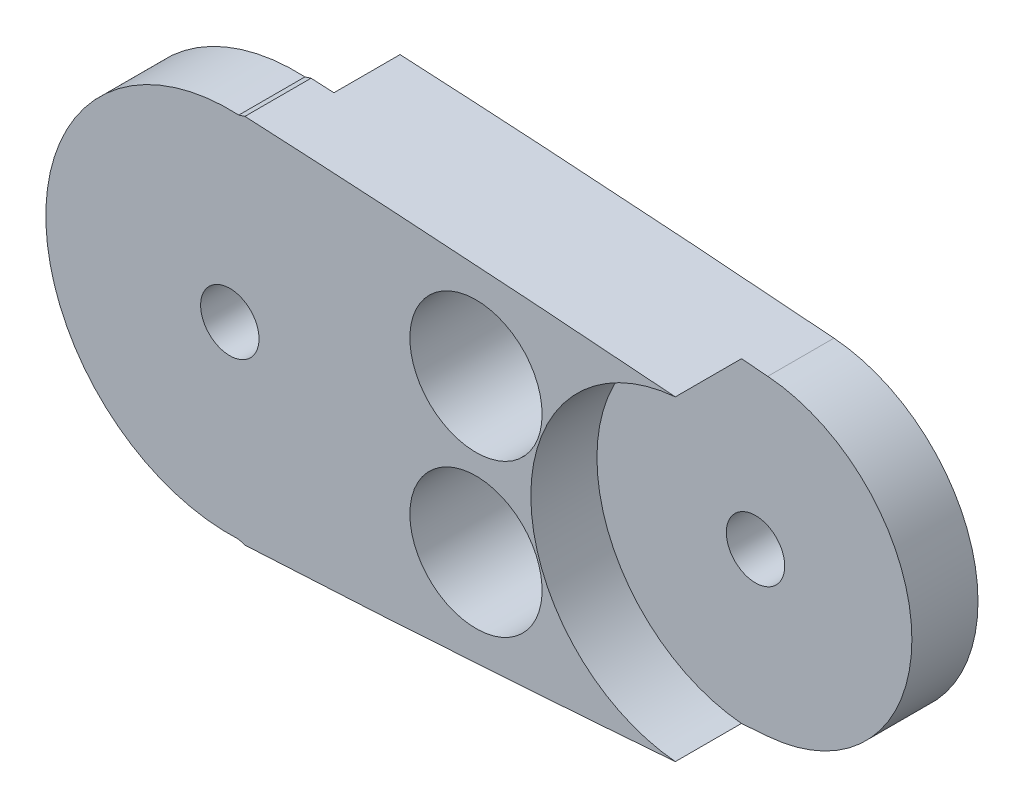
SolidWorks part; units mm, degrees
ref_plane "Front Plane" through (0, 0, 0) normal (0, 0, 1) x (1, 0, 0)
ref_plane "Top Plane" through (0, 0, 0) normal (0, 1, 0) x (1, 0, 0)
ref_plane "Right Plane" through (0, 0, 0) normal (1, 0, 0) x (0, 0, -1)
other "Center of Mass"
curve "Curve2"
  spline degree 3 poles (300, 0.378, 0) (299.8459, 0.3996, 0) (299.2303, 0.4859, 0) (297.8489, 0.6785, 0) (295.556, 0.9968, 0) (292.3657, 1.4334, 0) (288.2979, 1.9834, 0) (283.3772, 2.6357, 0) (277.6343, 3.3815, 0) (271.1045, 4.209, 0) (263.8281, 5.1072, 0) (255.8498, 6.0628, 0) (247.219, 7.0642, 0) (237.9888, 8.0979, 0) (228.216, 9.1511, 0) (217.9611, 10.2107, 0) (207.2872, 11.2632, 0) (196.2601, 12.2937, 0) (184.9478, 13.2887, 0) (173.4201, 14.2316, 0) (161.7479, 15.107, 0) (150.0032, 15.8986, 0) (138.2584, 16.5898, 0) (126.5858, 17.1634, 0) (115.0575, 17.6038, 0) (103.7442, 17.8968, 0) (92.7158, 18.028, 0) (82.0402, 17.9871, 0) (71.7831, 17.7661, 0) (62.0077, 17.3595, 0) (52.7741, 16.7661, 0) (44.1391, 15.9878, 0) (36.1555, 15.0306, 0) (28.872, 13.9026, 0) (22.3327, 12.6157, 0) (16.576, 11.1845, 0) (11.6345, 9.6228, 0) (7.5334, 7.9452, 0) (4.2857, 6.163, 0) (1.8965, 4.2728, 0) (0.3663, 2.2288, 0) (-0.1707, 0, 0) (0.3663, -2.2288, 0) (1.8965, -4.2728, 0) (4.2857, -6.163, 0) (7.5334, -7.9452, 0) (11.6345, -9.6228, 0) (16.576, -11.1845, 0) (22.3327, -12.6157, 0) (28.872, -13.9026, 0) (36.1555, -15.0306, 0) (44.1391, -15.9878, 0) (52.7741, -16.7661, 0) (62.0077, -17.3595, 0) (71.7831, -17.7661, 0) (82.0402, -17.9871, 0) (92.7158, -18.028, 0) (103.7442, -17.8968, 0) (115.0575, -17.6038, 0) (126.5858, -17.1634, 0) (138.2584, -16.5898, 0) (150.0032, -15.8986, 0) (161.7479, -15.107, 0) (173.4201, -14.2316, 0) (184.9478, -13.2887, 0) (196.2601, -12.2937, 0) (207.2872, -11.2632, 0) (217.9611, -10.2107, 0) (228.216, -9.1511, 0) (237.9888, -8.0979, 0) (247.219, -7.0642, 0) (255.8498, -6.0628, 0) (263.8281, -5.1072, 0) (271.1045, -4.209, 0) (277.6343, -3.3815, 0) (283.3772, -2.6357, 0) (288.2979, -1.9834, 0) (292.3657, -1.4334, 0) (295.556, -0.9968, 0) (297.8489, -0.6785, 0) (299.2303, -0.4859, 0) (299.8459, -0.3996, 0) (300, -0.378, 0) knots 0 0 0 0 0.000763 0.003048 0.006841 0.012116 0.018841 0.026973 0.03646 0.047243 0.059254 0.072417 0.086651 0.101866 0.117969 0.134858 0.152428 0.170572 0.189175 0.208122 0.227297 0.24658 0.265853 0.284997 0.303895 0.322433 0.340499 0.357984 0.374788 0.390812 0.405965 0.420162 0.433328 0.445394 0.456301 0.466004 0.474472 0.481696 0.487704 0.492583 0.496544 0.5 0.503456 0.507417 0.512296 0.518304 0.525528 0.533996 0.543699 0.554606 0.566672 0.579838 0.594035 0.609188 0.625212 0.642016 0.659501 0.677567 0.696105 0.715003 0.734147 0.75342 0.772703 0.791878 0.810825 0.829428 0.847572 0.865142 0.882031 0.898134 0.913349 0.927583 0.940746 0.952757 0.96354 0.973027 0.981159 0.987884 0.993159 0.996952 0.999237 1 1 1 1
sketch "Sketch2" plane through (0, 0, 0) normal (0, 0, 1) x (1, 0, 0)
  line L0 (0, 0) -> (300.3287, 0) construction
  line L9 (300, 0.378) -> (300, -0.378)
  line L17 (90, 18.0052) -> (90, -18.0052)
  line L20 (25.2817, 12.903) -> (25.2817, -12.903)
  line L21 (46.6322, 16.1183) -> (46.6322, -16.1183)
  line L22 (68.2099, 17.5933) -> (68.2099, -17.5933)
  line L23 (131.5031, 16.8963) -> (131.5031, -16.8963)
  line L24 (173.2123, 14.1909) -> (173.2123, -14.1909)
  line L25 (215.2898, -10.4186) -> (215.2898, 10.4186)
  line L26 (257.3103, -5.8439) -> (257.3103, 5.8439)
  arc A0 (300, -0.378) -> (300, 0.378) centre (299.947, 0) ccw
  arc A3 (45, 16.0354) -> (45, -16.0354) centre (46.6322, 0) ccw
  arc A5 (67.5, -17.5789) -> (67.5, 17.5789) centre (68.2099, 0) cw
  arc A6 (22.5, 12.5996) -> (22.5, -12.5996) centre (25.2817, 0) ccw
  arc A7 (258, -5.8031) -> (258, 5.8031) centre (257.3103, 0) cw
  arc A8 (216.3287, -10.3667) -> (216.3287, 10.3667) centre (215.2898, 0) cw
  arc A9 (174.3287, -14.147) -> (174.3287, 14.147) centre (173.2123, 0) cw
  arc A11 (132.3287, -16.8761) -> (132.3287, 16.8761) centre (131.5031, 0) cw
  arc A12 (90, -18.0052) -> (90, 18.0052) centre (89.9987, 0) cw
  arc A13 (22.5, 12.5996) -> (22.5, -12.5996) centre (25.2817, 0) cw
  arc A14 (45, 16.0354) -> (45, -16.0354) centre (46.6322, 0) cw
  arc A15 (67.5, 17.5789) -> (67.5, -17.5789) centre (68.2099, 0) cw
  arc A16 (90, -18.0052) -> (90, 18.0052) centre (90, 0) ccw
  arc A17 (132.3287, 16.8761) -> (132.3287, -16.8761) centre (131.5031, 0) cw
  arc A18 (174.3287, 14.147) -> (174.3287, -14.147) centre (173.2123, 0) cw
  arc A19 (216.3287, 10.3667) -> (216.3287, -10.3667) centre (215.2898, 0) cw
  arc A20 (257.9987, 5.8032) -> (257.9987, -5.8032) centre (257.309, 0) cw
  circle A21 centre (25.2817, 0) radius 12.903
  circle A22 centre (257.3103, 0) radius 5.8439
  circle A23 centre (25.2817, 0) radius 2.65
  circle A24 centre (8, 0) radius 2.65
  circle A25 centre (46.6322, 0) radius 2.65
  circle A26 centre (68.2099, 0) radius 2.65
  circle A27 centre (90, 0) radius 2.65
  circle A28 centre (131.5031, 0) radius 2.65
  circle A29 centre (173.2123, 0) radius 2.65
  circle A30 centre (215.2898, 0) radius 2.65
  spline S0 degree 3 poles (2737.659, 14788.0329) (538.1978, -52.3736) (419.7473, -16.3162) (297.8489, 0.6785) (295.556, 0.9968) (292.3657, 1.4334) (288.2979, 1.9834) (283.3772, 2.6357) (277.6343, 3.3815) (271.1045, 4.209) (263.8281, 5.1072) (255.8498, 6.0628) (247.219, 7.0642) (237.9888, 8.0979) (228.216, 9.1511) (217.9611, 10.2107) (207.2872, 11.2632) (196.2601, 12.2937) (184.9478, 13.2887) (173.4201, 14.2316) (161.7479, 15.107) (150.0032, 15.8986) (138.2584, 16.5898) (126.5858, 17.1634) (115.0575, 17.6038) (103.7442, 17.8968) (92.7158, 18.028) (82.0402, 17.9871) (71.7831, 17.7661) (62.0077, 17.3595) (52.7741, 16.7661) (44.1391, 15.9878) (36.1555, 15.0306) (28.872, 13.9026) (22.3327, 12.6157) (16.576, 11.1845) (11.6345, 9.6228) (7.5334, 7.9452) (4.2857, 6.163) (1.8965, 4.2728) (0.3663, 2.2288) (-0.1707, 0) (0.3663, -2.2288) (1.8965, -4.2728) (4.2857, -6.163) (7.5334, -7.9452) (11.6345, -9.6228) (16.576, -11.1845) (22.3327, -12.6157) (28.872, -13.9026) (36.1555, -15.0306) (44.1391, -15.9878) (52.7741, -16.7661) (62.0077, -17.3595) (71.7831, -17.7661) (82.0402, -17.9871) (92.7158, -18.028) (103.7442, -17.8968) (115.0575, -17.6038) (126.5858, -17.1634) (138.2584, -16.5898) (150.0032, -15.8986) (161.7479, -15.107) (173.4201, -14.2316) (184.9478, -13.2887) (196.2601, -12.2937) (207.2872, -11.2632) (217.9611, -10.2107) (228.216, -9.1511) (237.9888, -8.0979) (247.219, -7.0642) (255.8498, -6.0628) (263.8281, -5.1072) (271.1045, -4.209) (277.6343, -3.3815) (283.3772, -2.6357) (288.2979, -1.9834) (292.3657, -1.4334) (295.556, -0.9968) (297.8489, -0.6785) (419.7453, 16.3159) (538.1938, 52.3724) (2737.5472, -14787.2791) knots -0.59678 -0.59678 -0.59678 -0.59678 0.000763 0.003048 0.006841 0.012116 0.018841 0.026973 0.03646 0.047243 0.059254 0.072417 0.086651 0.101866 0.117969 0.134858 0.152428 0.170572 0.189175 0.208122 0.227297 0.24658 0.265853 0.284997 0.303895 0.322433 0.340499 0.357984 0.374788 0.390812 0.405965 0.420162 0.433328 0.445394 0.456301 0.466004 0.474472 0.481696 0.487704 0.492583 0.496544 0.5 0.503456 0.507417 0.512296 0.518304 0.525528 0.533996 0.543699 0.554606 0.566672 0.579838 0.594035 0.609188 0.625212 0.642016 0.659501 0.677567 0.696105 0.715003 0.734147 0.75342 0.772703 0.791878 0.810825 0.829428 0.847572 0.865142 0.882031 0.898134 0.913349 0.927583 0.940746 0.952757 0.96354 0.973027 0.981159 0.987884 0.993159 0.996952 0.999237 1.59677 1.59677 1.59677 1.59677 only from (300, 0.378) to (300, -0.378) construction
  spline S1 degree 3 poles (300, 0.378) (299.8459, 0.3996) (299.2303, 0.4859) (297.8489, 0.6785) (295.556, 0.9968) (292.3657, 1.4334) (288.2979, 1.9834) (283.3772, 2.6357) (277.6343, 3.3815) (271.1045, 4.209) (263.8281, 5.1072) (255.8498, 6.0628) (247.219, 7.0642) (237.9888, 8.0979) (228.216, 9.1511) (217.9611, 10.2107) (207.2872, 11.2632) (196.2601, 12.2937) (184.9478, 13.2887) (173.4201, 14.2316) (161.7479, 15.107) (150.0032, 15.8986) (138.2584, 16.5898) (126.5858, 17.1634) (115.0575, 17.6038) (103.7442, 17.8968) (92.7158, 18.028) (82.0402, 17.9871) (71.7831, 17.7661) (62.0077, 17.3595) (52.7741, 16.7661) (44.1391, 15.9878) (36.1555, 15.0306) (28.872, 13.9026) (22.3327, 12.6157) (16.576, 11.1845) (11.6345, 9.6228) (7.5334, 7.9452) (4.2857, 6.163) (1.8965, 4.2728) (0.3663, 2.2288) (-0.1707, 0) (0.3663, -2.2288) (1.8965, -4.2728) (4.2857, -6.163) (7.5334, -7.9452) (11.6345, -9.6228) (16.576, -11.1845) (22.3327, -12.6157) (28.872, -13.9026) (36.1555, -15.0306) (44.1391, -15.9878) (52.7741, -16.7661) (62.0077, -17.3595) (71.7831, -17.7661) (82.0402, -17.9871) (92.7158, -18.028) (103.7442, -17.8968) (115.0575, -17.6038) (126.5858, -17.1634) (138.2584, -16.5898) (150.0032, -15.8986) (161.7479, -15.107) (173.4201, -14.2316) (184.9478, -13.2887) (196.2601, -12.2937) (207.2872, -11.2632) (217.9611, -10.2107) (228.216, -9.1511) (237.9888, -8.0979) (247.219, -7.0642) (255.8498, -6.0628) (263.8281, -5.1072) (271.1045, -4.209) (277.6343, -3.3815) (283.3772, -2.6357) (288.2979, -1.9834) (292.3657, -1.4334) (295.556, -0.9968) (297.8489, -0.6785) (299.2303, -0.4859) (299.8459, -0.3996) (300, -0.378) knots 0 0 0 0 0.000763 0.003048 0.006841 0.012116 0.018841 0.026973 0.03646 0.047243 0.059254 0.072417 0.086651 0.101866 0.117969 0.134858 0.152428 0.170572 0.189175 0.208122 0.227297 0.24658 0.265853 0.284997 0.303895 0.322433 0.340499 0.357984 0.374788 0.390812 0.405965 0.420162 0.433328 0.445394 0.456301 0.466004 0.474472 0.481696 0.487704 0.492583 0.496544 0.5 0.503456 0.507417 0.512296 0.518304 0.525528 0.533996 0.543699 0.554606 0.566672 0.579838 0.594035 0.609188 0.625212 0.642016 0.659501 0.677567 0.696105 0.715003 0.734147 0.75342 0.772703 0.791878 0.810825 0.829428 0.847572 0.865142 0.882031 0.898134 0.913349 0.927583 0.940746 0.952757 0.96354 0.973027 0.981159 0.987884 0.993159 0.996952 0.999237 1 1 1 1
  point P47 (215.2898, 0)
  point P58 (257.3103, 0)
  point P61 (12.3787, 0)
  point P62 (62.7505, 0)
  dimension "D11" = 5.3
  dimension "D14" = 5.3
  dimension "D12" = 5.3
  dimension "D15" = 5.3
  dimension "D16" = 5.3
  dimension "D17" = 5.3
  dimension "D18" = 5.3
  dimension "D19" = 5.3
  dimension "D1" = 300.3287
  dimension "D2" = 89.9987
  dimension "D3" = 68.2099
  dimension "D4" = 46.6322
  dimension "D5" = 25.2817
  dimension "D6" = 168.8256
  dimension "D7" = 127.1164
  dimension "D8" = 85.0389
  dimension "D9" = 43.0184
  dimension "D10" = 50.3718
  dimension "D13" = 8
extrude "Boss-Extrude2" add sketch "Sketch2<21>" along normal blind 12 contours A17 L0 A9 S1 | L0 A17 S1 A9 region at (153.5826, 9.4965, 0) region at (153.5826, -9.4965, 0)
sketch "Sketch2<21>" plane through (0, 0, 0) normal (0, 0, 1) x (1, 0, 0) same geometry as "Sketch2"
extrude "Boss-Extrude3" add sketch "Sketch2" along normal blind 6 contours A9 L0 A29 L24 | L0 A9 L24 A29 | A29 L0 A18 A9 L24 | L0 A29 L24 A9 A18 region at (179.4121, 6.1998, 0) region at (179.4121, -6.1998, 0) region at (167.0125, 6.1998, 0) region at (167.0125, -6.1998, 0)
other "Center of Mass Reference Point1"
extrude "Boss-Extrude4" add sketch "Sketch2<24>" along normal blind 6 from offset 6 contours A28 L0 A17 A11 L23 | L0 A28 L23 A11 A17 | L0 A11 L23 A28 | A11 L0 A28 L23 region at (138.8266, 7.3235, 0) region at (138.8266, -7.3235, 0) region at (124.1796, 7.3235, 0) region at (124.1796, -7.3235, 0)
sketch "Sketch2<24>" plane through (0, 0, 0) normal (0, 0, 1) x (1, 0, 0) same geometry as "Sketch2"
sketch "Sketch4" plane through (0, 0, 6) normal (0, 0, 1) x (1, 0, 0)
  arc A0 (171.9352, 14.3342) -> (171.9352, -14.3342) centre (173.2123, 0) ccw
  arc A6 (174.3287, 14.147) -> (174.3287, -14.147) centre (173.2123, 0) ccw construction
  arc A7 (174.3287, 14.147) -> (174.3287, -14.147) centre (173.2123, 0) ccw
  spline S0 degree 3 poles (171.9352, -14.3342) (172.7331, -14.2723) (173.5309, -14.2099) (174.3287, -14.147) knots 0.789369 0.789369 0.789369 0.789369 0.793294 0.793294 0.793294 0.793294
  spline S2 degree 3 poles (174.3287, 14.147) (173.5309, 14.2099) (172.7331, 14.2723) (171.9352, 14.3342) knots 0.206706 0.206706 0.206706 0.206706 0.210631 0.210631 0.210631 0.210631
  spline S3 degree 3 poles (174.3287, 14.147) (173.5309, 14.2099) (172.7331, 14.2723) (171.9352, 14.3342) knots 0.206706 0.206706 0.206706 0.206706 0.210631 0.210631 0.210631 0.210631
  arc M5 (174.3287, 14.147) -> (174.3287, -14.147) centre (173.2123, 0) ccw
extrude "Cut-Extrude3" cut sketch "Sketch4" along normal through all contours S2 A0 S0 M5 region at (173.1294, 14.2085, 6)
sketch "Sketch5" plane through (0, 0, 6) normal (0, 0, -1) x (-1, 0, 0)
  arc A0 (-132.3287, 16.8761) -> (-132.3287, -16.8761) centre (-131.5031, 0) ccw construction
  arc A1 (-132.3287, 16.8761) -> (-132.3287, -16.8761) centre (-131.5031, 0) ccw
  arc A2 (-134.9523, 16.7448) -> (-134.9523, -16.7448) centre (-131.5031, 0) ccw
  arc A3 (-132.3385, 17.0759) -> (-132.3385, -17.0759) centre (-131.5031, 0) ccw construction
  spline S1 degree 3 poles (-134.9523, 16.7448) (-134.0778, 16.7896) (-133.2033, 16.8333) (-132.3287, 16.8761) knots 0.271221 0.271221 0.271221 0.271221 0.275515 0.275515 0.275515 0.275515
  spline S2 degree 3 poles (-132.3287, -16.8761) (-133.2033, -16.8333) (-134.0778, -16.7896) (-134.9523, -16.7448) knots 0.724485 0.724485 0.724485 0.724485 0.728779 0.728779 0.728779 0.728779
  arc M6 (-132.3287, 16.8761) -> (-132.3287, -16.8761) centre (-131.5031, 0) ccw
  dimension "D1" = 0.2
extrude "Cut-Extrude5" cut sketch "Sketch5" along normal through all contours S2 S1 A2 M6 region at (148.4369, 0, 6)
sketch "Sketch6" plane through (0, 0, 12) normal (0, 0, 1) x (1, 0, 0)
  line L0 (132.3221, 16.6762) -> (132.8764, 16.8492)
  line L1 (132.3189, -16.6764) -> (132.8764, -16.8492)
  arc A0 (132.3287, 16.8761) -> (132.3287, -16.8761) centre (131.5031, 0) ccw construction
  arc A1 (132.3287, 16.8761) -> (132.3287, -16.8761) centre (131.5031, 0) ccw
  arc A2 (132.3221, 16.6762) -> (132.3189, -16.6764) centre (131.5031, 0) ccw
  arc A3 (132.3189, 16.6764) -> (132.3189, -16.6764) centre (131.5031, 0) ccw construction
  spline S1 degree 3 poles (132.8764, 16.8492) (132.6938, 16.8582) (132.5113, 16.8672) (132.3287, 16.8761) knots 0.274619 0.274619 0.274619 0.274619 0.275515 0.275515 0.275515 0.275515
  spline S2 degree 3 poles (132.3287, -16.8761) (132.5113, -16.8672) (132.6938, -16.8582) (132.8764, -16.8492) knots 0.724485 0.724485 0.724485 0.724485 0.725381 0.725381 0.725381 0.725381
  spline M10 degree 3 poles (300, 0.378) (299.8459, 0.3996) (299.2303, 0.4859) (297.8489, 0.6785) (295.556, 0.9968) (292.3657, 1.4334) (288.2979, 1.9834) (283.3772, 2.6357) (277.6343, 3.3815) (271.1045, 4.209) (263.8281, 5.1072) (255.8498, 6.0628) (247.219, 7.0642) (237.9888, 8.0979) (228.216, 9.1511) (217.9611, 10.2107) (207.2872, 11.2632) (196.2601, 12.2937) (184.9478, 13.2887) (173.4201, 14.2316) (161.7479, 15.107) (150.0032, 15.8986) (138.2584, 16.5898) (126.5858, 17.1634) (115.0575, 17.6038) (103.7442, 17.8968) (92.7158, 18.028) (82.0402, 17.9871) (71.7831, 17.7661) (62.0077, 17.3595) (52.7741, 16.7661) (44.1391, 15.9878) (36.1555, 15.0306) (28.872, 13.9026) (22.3327, 12.6157) (16.576, 11.1845) (11.6345, 9.6228) (7.5334, 7.9452) (4.2857, 6.163) (1.8965, 4.2728) (0.3663, 2.2288) (-0.1707, 0) (0.3663, -2.2288) (1.8965, -4.2728) (4.2857, -6.163) (7.5334, -7.9452) (11.6345, -9.6228) (16.576, -11.1845) (22.3327, -12.6157) (28.872, -13.9026) (36.1555, -15.0306) (44.1391, -15.9878) (52.7741, -16.7661) (62.0077, -17.3595) (71.7831, -17.7661) (82.0402, -17.9871) (92.7158, -18.028) (103.7442, -17.8968) (115.0575, -17.6038) (126.5858, -17.1634) (138.2584, -16.5898) (150.0032, -15.8986) (161.7479, -15.107) (173.4201, -14.2316) (184.9478, -13.2887) (196.2601, -12.2937) (207.2872, -11.2632) (217.9611, -10.2107) (228.216, -9.1511) (237.9888, -8.0979) (247.219, -7.0642) (255.8498, -6.0628) (263.8281, -5.1072) (271.1045, -4.209) (277.6343, -3.3815) (283.3772, -2.6357) (288.2979, -1.9834) (292.3657, -1.4334) (295.556, -0.9968) (297.8489, -0.6785) (299.2303, -0.4859) (299.8459, -0.3996) (300, -0.378) knots 0 0 0 0 0.000763 0.003048 0.006841 0.012116 0.018841 0.026973 0.03646 0.047243 0.059254 0.072417 0.086651 0.101866 0.117969 0.134858 0.152428 0.170572 0.189175 0.208122 0.227297 0.24658 0.265853 0.284997 0.303895 0.322433 0.340499 0.357984 0.374788 0.390812 0.405965 0.420162 0.433328 0.445394 0.456301 0.466004 0.474472 0.481696 0.487704 0.492583 0.496544 0.5 0.503456 0.507417 0.512296 0.518304 0.525528 0.533996 0.543699 0.554606 0.566672 0.579838 0.594035 0.609188 0.625212 0.642016 0.659501 0.677567 0.696105 0.715003 0.734147 0.75342 0.772703 0.791878 0.810825 0.829428 0.847572 0.865142 0.882031 0.898134 0.913349 0.927583 0.940746 0.952757 0.96354 0.973027 0.981159 0.987884 0.993159 0.996952 0.999237 1 1 1 1 only from (132.3287, -16.8761) to (171.9352, -14.3342)
  spline M12 degree 3 poles (300, 0.378) (299.8459, 0.3996) (299.2303, 0.4859) (297.8489, 0.6785) (295.556, 0.9968) (292.3657, 1.4334) (288.2979, 1.9834) (283.3772, 2.6357) (277.6343, 3.3815) (271.1045, 4.209) (263.8281, 5.1072) (255.8498, 6.0628) (247.219, 7.0642) (237.9888, 8.0979) (228.216, 9.1511) (217.9611, 10.2107) (207.2872, 11.2632) (196.2601, 12.2937) (184.9478, 13.2887) (173.4201, 14.2316) (161.7479, 15.107) (150.0032, 15.8986) (138.2584, 16.5898) (126.5858, 17.1634) (115.0575, 17.6038) (103.7442, 17.8968) (92.7158, 18.028) (82.0402, 17.9871) (71.7831, 17.7661) (62.0077, 17.3595) (52.7741, 16.7661) (44.1391, 15.9878) (36.1555, 15.0306) (28.872, 13.9026) (22.3327, 12.6157) (16.576, 11.1845) (11.6345, 9.6228) (7.5334, 7.9452) (4.2857, 6.163) (1.8965, 4.2728) (0.3663, 2.2288) (-0.1707, 0) (0.3663, -2.2288) (1.8965, -4.2728) (4.2857, -6.163) (7.5334, -7.9452) (11.6345, -9.6228) (16.576, -11.1845) (22.3327, -12.6157) (28.872, -13.9026) (36.1555, -15.0306) (44.1391, -15.9878) (52.7741, -16.7661) (62.0077, -17.3595) (71.7831, -17.7661) (82.0402, -17.9871) (92.7158, -18.028) (103.7442, -17.8968) (115.0575, -17.6038) (126.5858, -17.1634) (138.2584, -16.5898) (150.0032, -15.8986) (161.7479, -15.107) (173.4201, -14.2316) (184.9478, -13.2887) (196.2601, -12.2937) (207.2872, -11.2632) (217.9611, -10.2107) (228.216, -9.1511) (237.9888, -8.0979) (247.219, -7.0642) (255.8498, -6.0628) (263.8281, -5.1072) (271.1045, -4.209) (277.6343, -3.3815) (283.3772, -2.6357) (288.2979, -1.9834) (292.3657, -1.4334) (295.556, -0.9968) (297.8489, -0.6785) (299.2303, -0.4859) (299.8459, -0.3996) (300, -0.378) knots 0 0 0 0 0.000763 0.003048 0.006841 0.012116 0.018841 0.026973 0.03646 0.047243 0.059254 0.072417 0.086651 0.101866 0.117969 0.134858 0.152428 0.170572 0.189175 0.208122 0.227297 0.24658 0.265853 0.284997 0.303895 0.322433 0.340499 0.357984 0.374788 0.390812 0.405965 0.420162 0.433328 0.445394 0.456301 0.466004 0.474472 0.481696 0.487704 0.492583 0.496544 0.5 0.503456 0.507417 0.512296 0.518304 0.525528 0.533996 0.543699 0.554606 0.566672 0.579838 0.594035 0.609188 0.625212 0.642016 0.659501 0.677567 0.696105 0.715003 0.734147 0.75342 0.772703 0.791878 0.810825 0.829428 0.847572 0.865142 0.882031 0.898134 0.913349 0.927583 0.940746 0.952757 0.96354 0.973027 0.981159 0.987884 0.993159 0.996952 0.999237 1 1 1 1 only from (171.9352, 14.3342) to (132.3287, 16.8761)
  arc M13 (132.3287, 16.8761) -> (132.3287, -16.8761) centre (131.5031, 0) ccw
  dimension "D1" = 0.2
extrude "Cut-Extrude6" cut sketch "Sketch6" against normal blind 10 contours A2 L0 L1 M12 M13 M10 region at (114.7684, 0.0016, 12)
sketch "Sketch7" plane through (0, 0, 12) normal (0, 0, 1) x (1, 0, 0)
  line L0 (114.8068, 0.0016) -> (199.5662, 0.0016) construction
  circle A2 centre (153.844, 6.9207) radius 6
  arc A3 (132.3221, 16.6762) -> (132.3189, -16.6764) centre (131.5031, 0) ccw construction
  circle A4 centre (153.844, -6.9176) radius 6
  point P9 (153.4124, 6.7849)
  point P10 (153.844, 6.9207)
  dimension "D1" = 12
extrude "Cut-Extrude7" cut sketch "Sketch7" against normal through all
